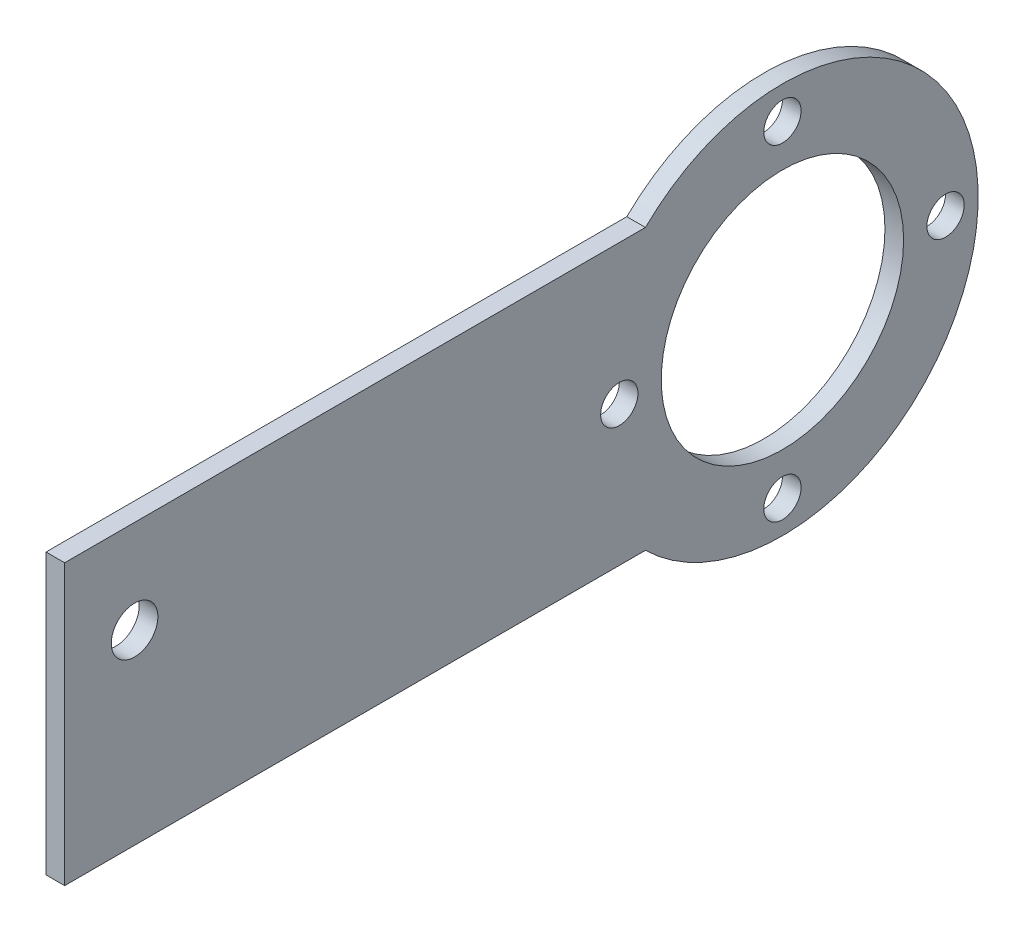
SolidWorks part; units mm, degrees
material "Thornel Mat VMA"
ref_plane "前视基准面" through (0, 0, 0) normal (0, 0, 1) x (1, 0, 0)
ref_plane "上视基准面" through (0, 0, 0) normal (0, 1, 0) x (1, 0, 0)
ref_plane "右视基准面" through (0, 0, 0) normal (1, 0, 0) x (0, 0, -1)
sketch "草图1" plane through (0, 0, 0) normal (1, 0, 0) x (0, 0, -1)
  line L1 (-105.3676, 55.4121) -> (-28.3676, 55.4121)
  line L2 (-105.3676, 55.4121) -> (-105.3676, 13.4121)
  line L3 (-105.3676, 13.4121) -> (-28.3676, 13.4121)
  arc A2 (-28.3676, 13.4121) -> (-28.3676, 55.4121) centre (-28.3676, 34.4121) ccw
extrude "凸台-拉伸1" add sketch "草图1" along normal blind 2 contours L1 A2 L3 L2
sketch "草图2" plane through (2, 0, 0) normal (1, 0, 0) x (0, 0, -1)
  line L0 (-67.0945, 19.4121) -> (-28.8676, 19.4121)
  line L1 (-105.3676, 55.4121) -> (-28.3676, 55.4121) construction
  line L2 (-47.8676, 13.4121) -> (-28.3676, 13.4121)
  line L3 (-105.3676, 55.4121) -> (-105.3676, 13.4121) construction
  line L4 (-105.3676, 13.4121) -> (-28.3676, 13.4121) construction
  line L5 (-28.8676, 19.4121) -> (-43.0645, 19.4121)
  line L6 (-47.8676, 13.4121) -> (-108.7654, 13.4121)
  line L8 (-47.8676, 19.4121) -> (-108.7654, 19.4121)
  line L9 (-108.7654, 13.4121) -> (-108.7654, 19.4121)
  line L10 (-43.0645, 49.4121) -> (-105.3676, 49.4121)
  line L11 (-105.3676, 49.4121) -> (-105.3676, 55.4121)
  line L12 (-105.3676, 55.4121) -> (-28.3676, 55.4121)
  line L13 (-45.8676, 34.4121) -> (-10.8676, 34.4121) construction
  line L14 (-28.3676, 51.9121) -> (-28.3676, 16.9121) construction
  circle A0 centre (-28.3676, 51.9121) radius 2
  circle A1 centre (-28.3676, 16.9121) radius 2
  circle A2 centre (-45.8676, 34.4121) radius 2
  circle A3 centre (-10.8676, 34.4121) radius 2
  circle A4 centre (-28.3676, 34.4121) radius 13
  arc A5 (-28.3676, 13.4121) -> (-43.0645, 19.4121) centre (-28.3676, 34.4121) cw
  arc A6 (-28.3676, 55.4121) -> (-43.0645, 49.4121) centre (-28.3676, 34.4121) ccw
  point P0 (-28.3676, 34.4121)
  line M1 (-105.3676, 55.4121) -> (-105.3676, 13.4121)
  line M2 (-105.3676, 13.4121) -> (-28.3676, 13.4121)
  line M4 (-28.3676, 55.4121) -> (-105.3676, 55.4121)
  dimension "D3" = 17.5
  dimension "D7" = 15
  dimension "D8" = 15
  dimension "D5" = 17.5
  dimension "D9" = 6
  dimension "D1" = 21
  dimension "D2" = 77
  dimension "D4" = 17.5
  dimension "D6" = 17.5
extrude "切除-拉伸1" cut sketch "草图2" against normal blind 3 contours A5 L5 L0 L8 M2 M1 | A2 | A0 | A3 | A1 | A4 region at (2, 16.3262, 71.8391)
extrude "切除-拉伸2" cut sketch "草图2<3>" against normal blind 10 contours A6 L10 M4 M1 region at (2, 52.4981, 71.8391)
sketch "草图2<3>" plane through (2, 0, 0) normal (1, 0, 0) x (0, 0, -1) same geometry as "草图2"
sketch "草图3" plane through (2, 0, 0) normal (1, 0, 0) x (0, 0, -1)
  line L0 (-105.3676, 19.4121) -> (-43.0645, 19.4121) construction
  line L1 (-105.3676, 49.4121) -> (-105.3676, 19.4121) construction
  circle A0 centre (-97.8676, 39.4121) radius 2.5
  dimension "D1" = 20
  dimension "D2" = 5
  dimension "D3" = 7.5
extrude "切除-拉伸4" cut sketch "草图3" against normal blind 10
